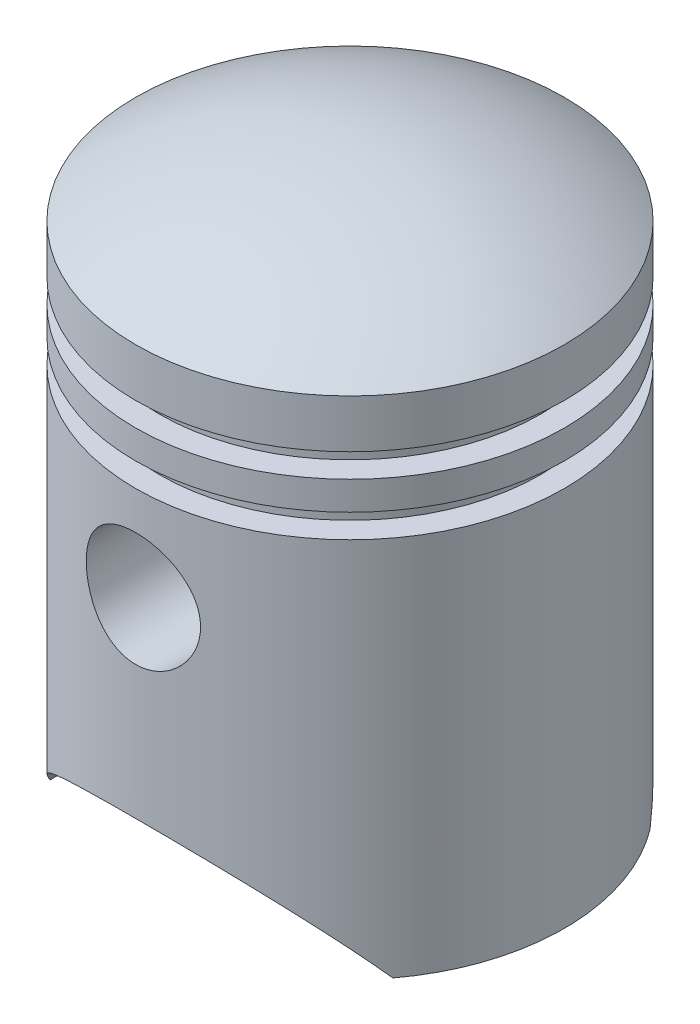
SolidWorks part; units mm, degrees
ref_plane "Płaszczyzna przednia" through (0, 0, 0) normal (0, 0, 1) x (1, 0, 0)
ref_plane "Płaszczyzna górna" through (0, 0, 0) normal (0, 1, 0) x (1, 0, 0)
ref_plane "Płaszczyzna prawa" through (0, 0, 0) normal (1, 0, 0) x (0, 0, -1)
sketch "Szkic1" plane through (0, 0, 0) normal (0, 0, 1) x (1, 0, 0)
  line L0 (0, 0) -> (0, 60)
  line L1 (0, 0) -> (22.5, 0)
  line L2 (22.5, 0) -> (22.5, 53.0719)
  arc A0 (0, 60) -> (22.5, 53.0719) centre (0, 20) cw
  point P3 (0, 20)
  dimension "D1" = 60
  dimension "D2" = 22.5
  dimension "D3" = 20
revolve "Obrót1" add sketch "Szkic1" angle 360 about L0
sketch "Szkic2" plane through (0, 0, 0) normal (0, 0, 1) x (1, 0, 0)
  line L0 (22.5, 0) -> (22.5, 53.0719) construction
  line L1 (22.5, 40) -> (20, 40)
  line L2 (22.5, 40) -> (22.5, 42.5)
  line L3 (22.5, 42.5) -> (20, 42.5)
  line L4 (20, 40) -> (20, 42.5)
  line L5 (0, 0) -> (0, 78.3491) construction
  dimension "D1" = 40
  dimension "D2" = 2.5
  dimension "D3" = 2.5
revolve "Wycięcie-obrót1" cut sketch "Szkic2" angle 360 about L5
pattern_linear "Szyk liniowy1" count 2 spacing 5.5 along (0, 1, 0) of "Wycięcie-obrót1"
shell "Skorupa1" thickness 2 removed face at (0, 0, -22.5)
sketch "Szkic3" plane through (0, 0, 0) normal (0, 0, 1) x (1, 0, 0)
  line L0 (-22.5, 0) -> (22.5, 0) construction
  arc A0 (-18, 0) -> (18, 0) centre (0, -11.2) cw
  point P3 (0, 0)
  point P7 (0, 10)
  dimension "D1" = 36
  dimension "D2" = 10
extrude "Wytnij-wyciągnięcie2" cut sketch "Szkic3" against normal through all both and the other way through all flip side to cut
sketch "Szkic4" plane through (0, 0, 0) normal (0, 0, 1) x (1, 0, 0)
  line L0 (0, 0) -> (0, 53.0719) construction
  line L1 (22.5, 53.0719) -> (-22.5, 53.0719) construction
  line L2 (22.5, 40) -> (-22.5, 40) construction
  circle A0 centre (0, 30) radius 6
  dimension "D1" = 10
  dimension "D2" = 12
extrude "Wytnij-wyciągnięcie3" cut sketch "Szkic4" against normal through all both and the other way through all
sketch "Szkic5" plane through (0, 0, 0) normal (0, 0, 1) x (1, 0, 0)
  circle A0 centre (0, 30) radius 7.5
  circle A1 centre (0, 30) radius 6 construction
  circle A2 centre (0, 30) radius 6
  dimension "D1" = 15
extrude "Dodanie-wyciągnięcie1" add sketch "Szkic5" along normal up to next from offset 10
mirror "Lustro1" about plane through (0, 0, 0) normal (0, 0, 1) of "Dodanie-wyciągnięcie1"
